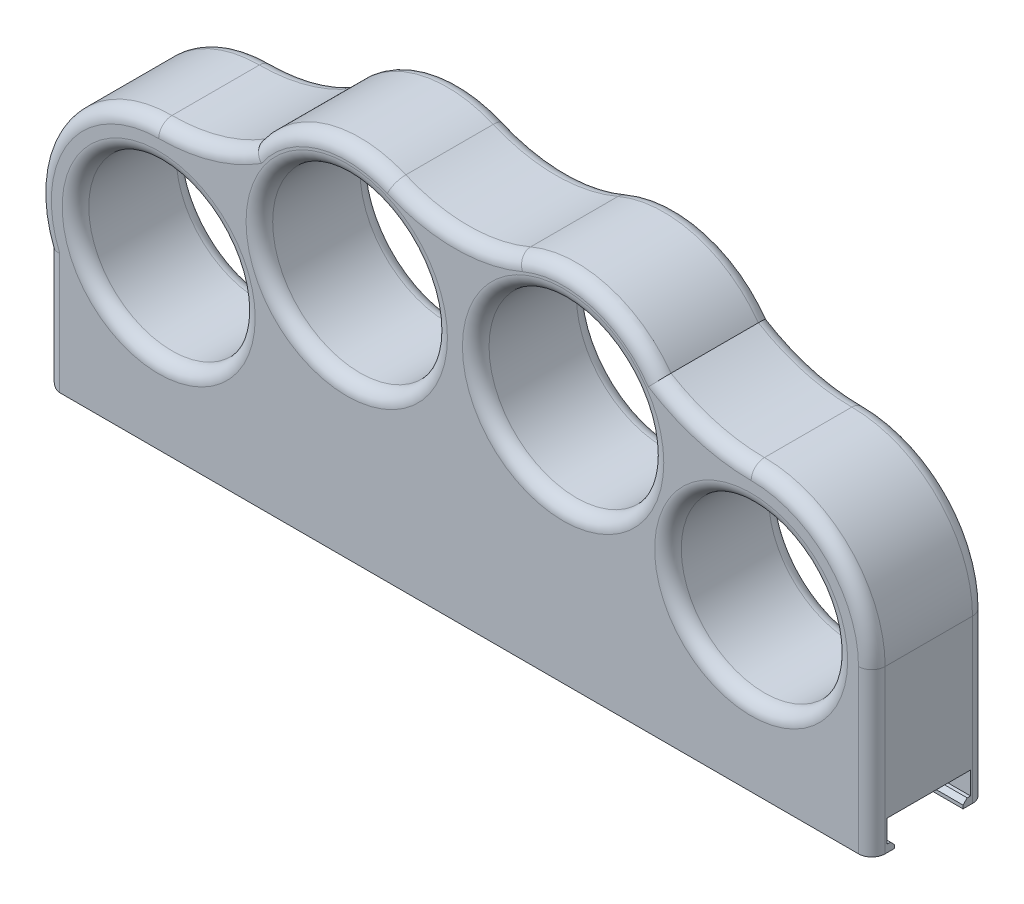
SolidWorks part; units mm, degrees
ref_plane "Alzado" through (0, 0, 0) normal (0, 0, 1) x (1, 0, 0)
ref_plane "Planta" through (0, 0, 0) normal (0, 1, 0) x (1, 0, 0)
ref_plane "Vista lateral" through (0, 0, 0) normal (1, 0, 0) x (0, 0, -1)
sketch "Croquis1" plane through (0, 0, 0) normal (0, 0, 1) x (1, 0, 0)
  line L0 (-49.1, -23) -> (-49.1, -25)
  line L3 (-47.1, -25) -> (50.1, -25)
  line L4 (50.1, -5.5) -> (50.1, -25)
  line L5 (-50.1, 25) -> (50.1, -25) construction
  line L6 (-50.1, -25) -> (50.1, 25) construction
  line L7 (-49.1, -10.7915) -> (-49.1, -23)
  line L8 (-49.1, -25) -> (-47.1, -25)
  circle A0 centre (-35.6, -5.5) radius 10
  circle A1 centre (35.6, -5.5) radius 10
  circle A2 centre (-13, 4) radius 10.5
  circle A3 centre (13, 4) radius 10.5
  arc A4 (-35.6, 9) -> (-49.1, -10.7915) centre (-35.6, -5.5) ccw
  arc A6 (50.1, -5.5) -> (35.6, 9) centre (35.6, -5.5) ccw
  arc A7 (24.3741, 12.1627) -> (7.4963, 16.8728) centre (13, 4) ccw
  arc A8 (-35.6, 9) -> (-24.3741, 12.1627) centre (-35.6, 30.5042) ccw
  arc A9 (35.6, 9) -> (24.3741, 12.1627) centre (35.6, 30.5042) cw
  arc A10 (-7.4963, 16.8728) -> (7.4963, 16.8728) centre (0, 34.4062) ccw
  arc A11 (23.3561, 2.2677) -> (21.4835, -2.187) centre (35.6, -5.5) ccw
  arc A12 (-7.4963, 16.8728) -> (-24.3741, 12.1627) centre (-13, 4) ccw
  point P0 (0, 0)
  point P33 (-49.1, -25)
  dimension "D3" = 20
  dimension "D6" = 20
  dimension "D9" = 21
  dimension "D12" = 21
  dimension "D15" = 29
  dimension "D17" = 29
  dimension "D18" = 28
  dimension "D1" = 100.2
  dimension "D2" = 50
  dimension "D4" = 19.5
  dimension "D5" = 14.5
  dimension "D7" = 19.5
  dimension "D8" = 14.5
  dimension "D10" = 26
  dimension "D13" = 29
  dimension "D19" = 1
extrude "Saliente-Extruir1" add sketch "Croquis1" along normal blind 13.7 contours A10 A12 A8 A4 L7 L3 L4 A6 A9 A7 A0 A1 A2 A3 region at (0.3346, -9.2749, 0)
fillet "Redondeo2" radius 1.6 8 edges at (45.6, -5.5, 0) (45.6, -5.5, 13.7) (23.5, 4, 0) (23.5, 4, 13.7) (-2.5, 4, 0) (-2.5, 4, 13.7) (-25.6, -5.5, 0) (-25.6, -5.5, 13.7)
ref_plane "Plano1" through (0, -25, 0) normal (0, -1, 0) x (-1, 0, 0)
sketch "Croquis2" plane through (0, -25, 0) normal (0, -1, 0) x (-1, 0, 0)
  line L0 (49.1, -13.7) -> (49.1, 0) construction
  line L1 (39.1, -11.86) -> (-50.1, -11.86)
  line L2 (39.1, -11.86) -> (39.1, -1.84)
  line L3 (39.1, -1.84) -> (-50.1, -1.84)
  line L4 (-50.1, -11.86) -> (-50.1, -1.84)
  line L5 (-50.1, -13.7) -> (-50.1, 0) construction
  dimension "D1" = 10
  dimension "D2" = 1.84
  dimension "D3" = 1.84
extrude "Cortar-Extruir1" cut sketch "Croquis2" against normal blind 3.6
ref_plane "Plano2" through (0, -25, 0) normal (0, -1, 0) x (-1, 0, 0)
sketch "Croquis3" plane through (0, -25, 0) normal (0, -1, 0) x (-1, 0, 0)
  line L0 (39.1, -11.86) -> (39.1, -1.84) construction
  line L1 (-50.1, -11.86) -> (39.1, -11.86)
  line L2 (-50.1, -11.86) -> (-50.1, -10.96)
  line L3 (-50.1, -10.96) -> (39.1, -10.96)
  line L4 (39.1, -11.86) -> (39.1, -10.96)
  line L6 (-50.1, -1.84) -> (39.1, -1.84)
  line L7 (-50.1, -1.84) -> (-50.1, -2.74)
  line L8 (-50.1, -2.74) -> (39.1, -2.74)
  line L9 (39.1, -1.84) -> (39.1, -2.74)
  line L10 (39.1, -10.96) -> (37.1, -10.96)
  line L11 (39.1, -10.96) -> (39.1, -2.74)
  line L12 (39.1, -2.74) -> (37.1, -2.74)
  line L13 (37.1, -10.96) -> (37.1, -2.74)
  dimension "D1" = 0.9
  dimension "D2" = 0.9
  dimension "D3" = 2
extrude "Saliente-Extruir3" add sketch "Croquis3" against normal blind 0.8999 contours L9 L6 L7 L8 | L1 L4 L3 L2 | L13 L3 L11 L8 region at (5.5, -25, 11.41) region at (-38.1, -25, 6.85) region at (5.5, -25, 2.29)
chamfer "Chaflán1" distance 0.5 angle 45 2 edges at (6.5, -24.1001, 10.96) (6.5, -24.1001, 2.74)
fillet "Redondeo6" radius 1.6 19 edges at (29.7685, 9.8058, 0) (45.853, 4.753, 0) (29.7685, 9.8058, 13.7) (45.853, 4.753, 13.7) (50.1, -15.25, 0) (50.1, -15.25, 13.7) (-29.7685, 9.8058, 13.7) (-29.7685, 9.8058, 0) (-49.1, -17.8958, 0) (-47.5787, 2.6708, 13.7) (-47.5787, 2.6708, 0) (-49.1, -17.8958, 13.7) (-16.7632, 17.4847, 13.7) (0, 15.3375, 13.7) (16.7632, 17.4847, 0) (0, 15.3375, 0) (-49.1, -25, 6.85) (16.7632, 17.4847, 13.7) (-16.7632, 17.4847, 0)
chamfer "Chaflán3" distance 0.5 angle 45 1 edges at (-37.1, -24.1001, 6.85)
